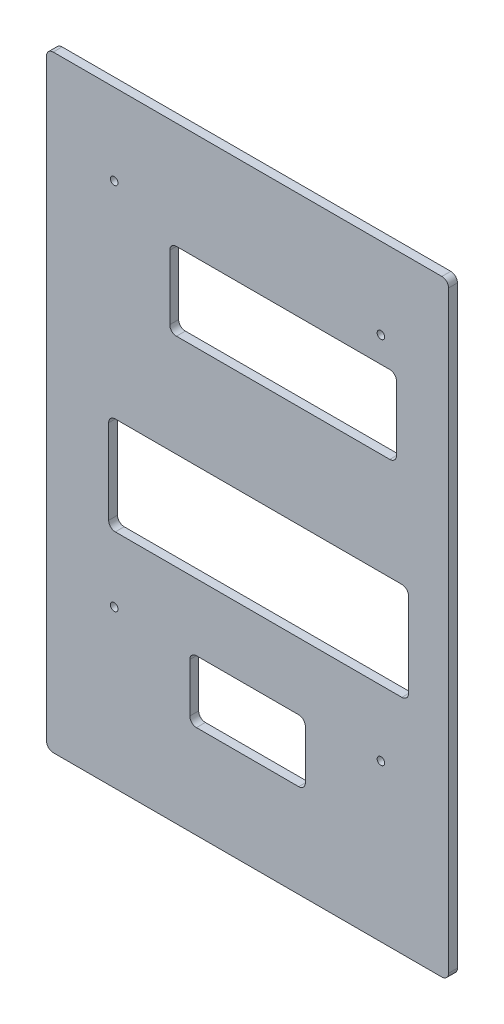
SolidWorks part; units mm, degrees
material "Verre"
ref_plane "Plan de face" through (0, 0, 0) normal (0, 0, 1) x (1, 0, 0)
ref_plane "Plan de dessus" through (0, 0, 0) normal (0, 1, 0) x (1, 0, 0)
ref_plane "Plan de droite" through (0, 0, 0) normal (1, 0, 0) x (0, 0, -1)
sketch "Esquisse1" plane through (0, 0, 0) normal (0, 0, 1) x (1, 0, 0)
  line L1 (0, 0) -> (180.86, 0)
  line L2 (0, 0) -> (0, 273)
  line L3 (0, 273) -> (180.86, 273)
  line L4 (180.86, 0) -> (180.86, 273)
  line L5 (64.43, 70) -> (116.43, 70)
  line L6 (64.43, 70) -> (64.43, 42)
  line L7 (64.43, 42) -> (116.43, 42)
  line L8 (116.43, 70) -> (116.43, 42)
  line L9 (27.93, 144) -> (162.86, 144)
  line L10 (27.93, 144) -> (27.93, 100)
  line L11 (27.93, 100) -> (162.86, 100)
  line L12 (162.86, 144) -> (162.86, 100)
  line L13 (55.43, 225) -> (157.43, 225)
  line L14 (55.43, 225) -> (55.43, 190)
  line L15 (55.43, 190) -> (157.43, 190)
  line L16 (157.43, 225) -> (157.43, 190)
  circle A0 centre (30.43, 236.5) radius 1.5
  circle A1 centre (150.43, 236.5) radius 1.5
  circle A2 centre (30.43, 70.5) radius 1.5
  circle A3 centre (150.43, 70.5) radius 1.5
  dimension "D5" = 3
  dimension "D8" = 3
  dimension "D13" = 3
  dimension "D14" = 3
  dimension "D1" = 180.86
  dimension "D2" = 273
  dimension "D3" = 30.43
  dimension "D4" = 36.5
  dimension "D6" = 36.5
  dimension "D7" = 30.43
  dimension "D9" = 30.43
  dimension "D10" = 30.43
  dimension "D11" = 70.5
  dimension "D12" = 70.5
  dimension "D15" = 64.43
  dimension "D16" = 42
  dimension "D17" = 28
  dimension "D18" = 30
  dimension "D19" = 44
  dimension "D20" = 52
  dimension "D21" = 27.93
  dimension "D22" = 18
  dimension "D23" = 48
  dimension "D24" = 35
  dimension "D25" = 55.43
  dimension "D26" = 102
extrude "Boss.-Extru.1" add sketch "Esquisse1" along normal blind 4
hole_wizard "Dégagement M31" positions "Esquisse2" profile "Esquisse3" hole size "M3" standard "ISO" end condition through all
sketch "Esquisse2" plane through (0, 0, 4) normal (0, 0, 1) x (1, 0, 0)
  point P0 (30.43, 236.5)
  point P3 (150.43, 236.5)
  point P6 (150.43, 70.5)
  point P9 (30.43, 70.5)
sketch "Esquisse3" plane through (30.43, 236.5, 4) normal (1, 0, 0) x (0, -1, 0)
  line L0 (0, 0) -> (0, 4)
  line L1 (0, 4) -> (1.7, 4)
  line L2 (1.7, 4) -> (1.7, 0)
  line L5 (1.7, 0) -> (0, 0)
  line L11 (0, -6.35) -> (0, 107.95) construction
  dimension "Diamètre du perçage jusqu'au prochain" = 3.4
  dimension "Profondeur du perçage jusqu'au prochain" = 4
fillet "Congé1" radius 3 16 edges at (0, 0, 2) (180.86, 0, 2) (116.43, 42, 2) (64.43, 42, 2) (116.43, 70, 2) (64.43, 70, 2) (162.86, 100, 2) (27.93, 100, 2) (162.86, 144, 2) (27.93, 144, 2) (180.86, 273, 2) (0, 273, 2) (157.43, 190, 2) (157.43, 225, 2) (55.43, 225, 2) (55.43, 190, 2)
sketch "Esquisse4" [suppressed] plane through (0, 0, 4) normal (0, 0, 1) x (1, 0, 0)
  line L0 (27.93, 165) -> (162.86, 165) construction
  line L1 (58.43, 190) -> (154.43, 190) construction
  line L3 (27.93, 165) -> (27.93, 135.3531) construction
  line L4 (162.86, 165) -> (162.86, 135.3531) construction
  line L5 (27.93, 141) -> (27.93, 103) construction
  line L6 (162.86, 103) -> (162.86, 141) construction
  point P5 (27.93, 135.3531)
  point P9 (162.86, 135.3531)
  dimension "D1" = 25
sketch "Esquisse5" plane through (0, 0, 0) normal (0, 0, -1) x (-1, 0, 0)
  line L0 (-56.9089, 202.3439) -> (421.0911, 202.3439) construction
  line L1 (107.0911, 240.8566) -> (1241.0911, 240.8566) construction
  line L2 (-94.2833, 174.0347) -> (-91.1852, 174.0347)
  line L3 (-91.1852, 174.0347) -> (-91.1824, 166.7906)
  line L4 (-84.6968, 170.3369) -> (-88.3318, 166.2594)
  line L5 (-88.3318, 166.2594) -> (-84.4535, 160.0184)
  line L6 (-84.4535, 160.0184) -> (-87.9228, 160.0184)
  line L7 (-87.9228, 160.0184) -> (-90.4278, 164.3432)
  line L8 (-91.1824, 160.0184) -> (-94.2833, 160.0184)
  line L9 (-94.2833, 160.0184) -> (-94.2833, 174.0347)
  line L10 (-78.7925, 174.0347) -> (-75.6893, 174.0347)
  line L11 (-75.6893, 174.0347) -> (-75.6893, 169.1495)
  line L12 (-69.5264, 160.0184) -> (-72.6249, 160.0184)
  line L13 (-75.6943, 160.0184) -> (-78.7925, 160.0184)
  line L14 (-78.7925, 160.0184) -> (-78.7925, 174.0347)
  line L15 (-139.2569, 172.9353) -> (-137.1581, 172.9353)
  line L16 (-137.1581, 172.9353) -> (-137.1581, 170.4368)
  line L17 (-137.1581, 170.4368) -> (-133.6735, 170.4368)
  line L18 (-133.6735, 170.4368) -> (-133.6735, 168.1381)
  line L19 (-133.6735, 168.1381) -> (-137.1581, 168.1381)
  line L20 (-137.1581, 168.1381) -> (-137.1581, 162.8704)
  line L21 (-133.2794, 162.5414) -> (-133.2794, 160.2428)
  line L22 (-140.1754, 168.1381) -> (-141.7532, 168.1381)
  line L23 (-141.7532, 168.1381) -> (-141.7532, 170.3369)
  line L24 (-141.7532, 170.3369) -> (-140.0239, 170.3369)
  line L25 (-140.0239, 170.3369) -> (-139.2569, 172.9353)
  line L26 (-12.9312, 172.9353) -> (-10.9324, 172.8354)
  line L27 (-10.9324, 172.8354) -> (-10.8324, 170.4368)
  line L28 (-10.8324, 170.4368) -> (-7.4344, 170.4368)
  line L29 (-7.4344, 170.4368) -> (-7.4344, 168.1381)
  line L30 (-7.4344, 168.1381) -> (-10.9324, 168.1381)
  line L31 (-10.9324, 168.1381) -> (-10.8324, 162.5414)
  line L32 (-57.505, 164.5403) -> (-59.1422, 164.5403)
  line L33 (-7.0347, 162.4415) -> (-7.0347, 160.2428)
  line L34 (-13.8145, 168.2381) -> (-15.4406, 168.2381)
  line L35 (-15.4406, 168.2381) -> (-15.4406, 170.4368)
  line L36 (-15.4406, 170.4368) -> (-13.7165, 170.4368)
  line L37 (-13.7165, 170.4368) -> (-12.9312, 172.9353)
  line L38 (-174.2363, 172.8354) -> (-163.6381, 172.8354)
  line L39 (-163.6381, 172.8354) -> (-163.6381, 170.2335)
  line L40 (-163.6381, 170.2335) -> (-167.3327, 170.2335)
  line L41 (-167.3327, 170.2335) -> (-167.3327, 160.0184)
  line L42 (-167.3327, 160.0184) -> (-170.5222, 160.0184)
  line L43 (-170.5222, 160.0184) -> (-170.5703, 170.2335)
  line L44 (-170.5703, 170.2335) -> (-174.2363, 170.2335)
  line L45 (-174.2363, 170.2335) -> (-174.2363, 172.8354)
  line L46 (-47.2135, 160.0661) -> (-47.2135, 172.8354)
  line L47 (-27.5226, 172.1358) -> (-25.224, 172.0359)
  line L48 (-25.224, 172.0359) -> (-24.9241, 170.6367)
  line L49 (-22.8254, 171.1364) -> (-21.1497, 169.4374)
  line L50 (-21.6333, 167.3283) -> (-20.2269, 167.1387)
  line L51 (-20.2269, 167.1387) -> (-20.3269, 164.8401)
  line L52 (-20.3269, 164.8401) -> (-21.726, 164.5403)
  line L53 (-21.3263, 162.4415) -> (-22.9253, 160.8424)
  line L54 (-22.9253, 160.8424) -> (-24.1246, 161.642)
  line L55 (-25.0241, 161.2422) -> (-25.3239, 159.843)
  line L56 (-25.3239, 159.843) -> (-27.5226, 159.943)
  line L57 (-27.5226, 159.943) -> (-27.8224, 161.3421)
  line L58 (-29.9212, 160.9424) -> (-31.5203, 162.5414)
  line L59 (-31.5203, 162.5414) -> (-30.7207, 163.7407)
  line L60 (-31.1205, 164.6402) -> (-32.5197, 164.94)
  line L61 (-32.5197, 164.94) -> (-32.4197, 167.1387)
  line L62 (-32.4197, 167.1387) -> (-31.0206, 167.4386)
  line L63 (-30.7207, 168.338) -> (-31.5203, 169.5373)
  line L64 (-31.5203, 169.5373) -> (-29.9212, 171.0364)
  line L65 (-27.8224, 170.6367) -> (-27.5226, 172.1358)
  line L66 (-121.3674, 171.736) -> (-113.2722, 160.1428)
  line L67 (-113.2722, 160.1428) -> (-130.1622, 160.2428)
  line L68 (-130.1622, 160.2428) -> (-121.3674, 171.736)
  line L69 (-101.122, 160.0184) -> (-104.166, 160.0184)
  line L70 (-107.2724, 160.0184) -> (-110.3739, 160.0184)
  line L71 (-110.3739, 160.0184) -> (-110.3739, 170.4368)
  line L72 (-110.3739, 170.4368) -> (-107.471, 170.4368)
  line L73 (-107.2724, 169.1495) -> (-107.471, 169.1495)
  line L74 (-55.5361, 159.943) -> (-54.06, 159.943)
  line L75 (-53.0008, 162.1272) -> (-53.0008, 160.2428)
  line L76 (-57.4815, 166.5394) -> (-57.4815, 167.3283)
  line L77 (-59.7101, 167.0388) -> (-62.9094, 167.1387)
  line L78 (-157.7434, 170.3369) -> (-154.6917, 170.352)
  line L79 (-151.8049, 170.352) -> (-148.7513, 170.3369)
  line L80 (-148.7513, 170.3369) -> (-148.6473, 160.0184)
  line L81 (-148.6473, 160.0184) -> (-151.6216, 160.0184)
  line L82 (-151.6216, 160.0184) -> (-151.6216, 161.4269)
  line L83 (-122.8785, 167.7334) -> (-124.9653, 161.2422)
  line L84 (-124.9653, 161.2422) -> (-127.9635, 161.3421)
  line L85 (-127.9635, 161.3421) -> (-122.8785, 167.7334)
  line L86 (-121.2675, 169.4374) -> (-115.4709, 161.3421)
  line L87 (-115.4709, 161.3421) -> (-123.6661, 161.3421)
  line L88 (-123.6661, 161.3421) -> (-121.2675, 169.4374)
  line L89 (-44.0087, 167.9383) -> (-44.0087, 170.3369)
  line L90 (-44.0267, 165.4648) -> (-44.0267, 162.5414)
  line L91 (-44.0267, 162.5414) -> (-41.8105, 162.5414)
  line L92 (-41.8105, 165.4648) -> (-44.0267, 165.4648)
  line L93 (-22.0456, 168.2381) -> (-21.1497, 169.4374)
  line L94 (-22.0456, 168.2381) -> (-21.6333, 167.3283)
  line L95 (-25.0241, 161.2422) -> (-24.1246, 161.642)
  line L96 (-31.1205, 164.6402) -> (-30.7207, 163.7407)
  line L97 (-30.7207, 168.338) -> (-31.0206, 167.4386)
  line L98 (-60.0892, 163.7407) -> (-60.0892, 162.8704)
  line L99 (-57.505, 164.5403) -> (-57.505, 163.8272)
  line L100 (-154.6917, 170.352) -> (-154.6917, 164.3054)
  line L101 (-151.8049, 170.352) -> (-151.8049, 164.3054)
  line L102 (-107.471, 169.1495) -> (-107.471, 170.4368)
  line L103 (-101.122, 160.0184) -> (-101.122, 167.4386)
  line L104 (-104.166, 160.0184) -> (-104.166, 165.9507)
  line L105 (-107.2724, 160.0184) -> (-107.2724, 165.9507)
  line L106 (-84.6968, 170.3369) -> (-88.0776, 170.3369)
  line L107 (-88.0776, 170.3369) -> (-91.1824, 166.7906)
  line L108 (-91.1824, 160.0184) -> (-91.1824, 163.8272)
  line L109 (-91.1824, 163.8272) -> (-90.4278, 164.3432)
  line L110 (-75.6943, 160.0184) -> (-75.6943, 165.9507)
  line L111 (-72.6249, 160.0184) -> (-72.6249, 166.7906)
  line L112 (-69.5264, 160.0184) -> (-69.5264, 167.4386)
  line L113 (-54.4145, 167.0061) -> (-54.4145, 162.6507)
  line L114 (-47.2135, 172.8354) -> (-41.5192, 172.8354)
  line L115 (-47.2135, 160.0661) -> (-40.67, 160.0661)
  line L116 (-44.0087, 170.3369) -> (-42.1743, 170.3369)
  line L117 (-44.0087, 167.9383) -> (-42.0498, 167.9383)
  arc A0 (-59.1422, 164.5403) -> (-60.0892, 163.7407) centre (-59.1422, 163.5797) ccw
  circle A1 centre (-26.3868, 165.9832) radius 2.3707
  arc A2 (-41.8105, 162.5414) -> (-41.8105, 165.4648) centre (-41.8105, 164.0031) ccw
  spline S0 degree 3 poles (-75.6943, 165.9507) (-75.607, 166.6089) (-75.1986, 167.568) (-73.6088, 168.4964) (-72.5255, 167.5211) (-72.6249, 166.7906) knots 0 0 0 0 0.394541 0.59607 1 1 1 1
  spline S1 degree 3 poles (-75.6893, 169.1495) (-75.2594, 169.7597) (-73.9101, 170.5281) (-70.9079, 170.7231) (-69.5421, 168.6416) (-69.5264, 167.4386) knots 0 0 0 0 0.262741 0.558365 1 1 1 1
  spline S2 degree 3 poles (-54.4145, 162.6507) (-54.3978, 162.4449) (-54.1312, 161.7319) (-53.3221, 162.0376) (-53.0008, 162.1272) knots 0 0 0 0 0.373122 1 1 1 1
  spline S3 degree 3 poles (-57.0864, 161.3421) (-56.9419, 160.6025) (-56.2449, 160.0799) (-55.5361, 159.943) knots 0 0 0 0 1 1 1 1
  spline S4 degree 3 poles (-137.1581, 162.8704) (-137.1357, 162.6205) (-136.8298, 162.3293) (-135.4596, 161.9489) (-134.2298, 162.3066) (-133.2794, 162.5414) knots 0 0 0 0 0.163675 0.27749 1 1 1 1
  spline S5 degree 3 poles (-133.2794, 160.2428) (-134.8141, 160.051) (-138.7019, 159.2323) (-139.6757, 161.3421) (-139.8081, 161.6291) (-139.9498, 161.9266) (-139.9755, 162.2416) (-140.1355, 164.2017) (-140.072, 166.1742) (-140.1754, 168.1381) knots 0 0 0 0 1 1 1 2 2 2 3 3 3 3
  spline S6 degree 3 poles (-7.0347, 160.2428) (-8.6244, 160.0676) (-12.4699, 159.3084) (-13.4142, 161.4355) (-13.624, 161.9082) (-13.782, 162.4232) (-13.792, 162.9403) (-13.826, 164.7059) (-13.807, 166.4722) (-13.8145, 168.2381) knots 0 0 0 0 1 1 1 2 2 2 3 3 3 3
  spline S7 degree 3 poles (-40.67, 160.0661) (-39.7367, 160.1577) (-38.4804, 160.8468) (-37.2595, 162.3426) (-37.1701, 163.6675) (-37.1743, 165.538) (-38.7166, 166.4794) (-39.5286, 166.7906) knots 0 0 0 0 0.282707 0.43558 0.571416 0.685536 1 1 1 1
  spline S8 degree 3 poles (-39.5286, 166.7906) (-38.9565, 166.948) (-38.2374, 167.6832) (-37.8968, 168.9733) (-37.8113, 170.1278) (-38.2848, 171.2576) (-39.48, 172.3911) (-40.6921, 172.7767) (-41.5192, 172.8354) knots 0 0 0 0 0.199158 0.317575 0.451003 0.584991 0.71822 1 1 1 1
  spline S9 degree 3 poles (-24.9241, 170.6367) (-23.5477, 170.1779) (-23.8936, 170.4242) (-22.8254, 171.1364) knots 0 0 0 0 1 1 1 1
  spline S10 degree 3 poles (-21.726, 164.5403) (-22.2066, 163.0985) (-21.9033, 163.5956) (-21.3263, 162.4415) knots 0 0 0 0 1 1 1 1
  spline S11 degree 3 poles (-27.8224, 161.3421) (-28.7992, 161.6677) (-28.5552, 161.7587) (-29.2216, 161.3421) (-29.4494, 161.1998) (-29.688, 161.0756) (-29.9212, 160.9424) knots 0 0 0 0 1 1 1 2 2 2 2
  spline S12 degree 3 poles (-29.9212, 171.0364) (-29.4943, 170.8941) (-29.1686, 170.3865) (-28.7219, 170.3369) (-28.3801, 170.2989) (-28.1209, 170.5372) (-27.8224, 170.6367) knots 0 0 0 0 1 1 1 2 2 2 2
  spline S13 degree 3 poles (-107.2724, 169.1495) (-106.8585, 169.8299) (-105.5179, 170.598) (-103.5202, 170.6358) (-101.6572, 169.6874) (-101.1521, 168.2861) (-101.122, 167.4386) knots 0 0 0 0 0.27864 0.525252 0.687769 1 1 1 1
  spline S14 degree 3 poles (-107.2724, 165.9507) (-107.2465, 166.745) (-106.2762, 168.5882) (-104.0431, 167.7417) (-104.2041, 166.4557) (-104.166, 165.9507) knots 0 0 0 0 0.496685 0.694227 1 1 1 1
  spline S15 degree 2 poles (-54.06, 159.943) (-53.5081, 160.0158) (-53.0008, 160.2428) knots 0 0 0 1 1 1
  spline S16 degree 3 poles (-59.7101, 167.0388) (-59.773, 167.4531) (-59.3518, 168.8785) (-57.4745, 168.3639) (-57.4815, 167.3283) knots 0 0 0 0 0.367002 1 1 1 1
  spline S17 degree 3 poles (-57.0864, 161.3421) (-57.3774, 161.0516) (-57.8191, 160.5577) (-58.1867, 160.3437) (-59.3607, 159.6603) (-61.068, 159.6271) (-62.1842, 160.4472) (-63.7018, 161.5622) (-63.6714, 164.6228) (-62.0796, 165.6441) (-60.7256, 166.5129) (-59.0024, 166.4238) (-57.4815, 166.5394) knots 0 0 0 0 1 1 1 2 2 2 3 3 3 4 4 4 4
  spline S18 degree 3 poles (-62.9094, 167.1387) (-62.8636, 167.8511) (-62.16, 169.9427) (-59.8154, 170.6023) (-58.5702, 170.5768) knots 0 0 0 0 0.353066 1 1 1 1
  spline S19 degree 3 poles (-154.6917, 164.3054) (-154.7394, 163.7332) (-154.5444, 163.0059) (-153.7633, 162.1776) (-152.8735, 162.3733) (-152.0344, 163.0441) (-151.8568, 163.8566) (-151.8049, 164.3054) knots 0 0 0 0 0.303187 0.415254 0.583999 0.737935 1 1 1 1
  spline S20 degree 3 poles (-151.6216, 161.4269) (-151.9172, 161.1229) (-152.1728, 160.7741) (-152.5084, 160.515) (-152.7443, 160.3329) (-153.0209, 160.2022) (-153.3023, 160.1041) (-155.6394, 159.2885) (-157.5509, 160.7972) (-157.6441, 163.2417) (-157.7341, 165.6053) (-157.7103, 167.9718) (-157.7434, 170.3369) knots 0 0 0 0 1 1 1 2 2 2 3 3 3 4 4 4 4
  spline S21 degree 3 poles (-42.0498, 167.9383) (-41.6698, 167.9271) (-41.2486, 168.3464) (-41.0744, 169.1173) (-41.2166, 169.9639) (-41.8255, 170.2992) (-42.1743, 170.3369) knots 0 0 0 0 0.294875 0.472372 0.68529 1 1 1 1
  spline S23 degree 3 poles (-7.0347, 162.4415) (-7.8006, 162.2378) (-9.0559, 162.1282) (-10.4545, 162.0729) (-10.8324, 162.5414) knots 0 0 0 0 0.590902 1 1 1 1
  spline S24 degree 3 poles (-57.505, 163.8272) (-57.5306, 163.3193) (-57.9984, 162.5511) (-59.1839, 162.1257) (-60.0621, 162.2684) (-60.0892, 162.8704) knots 0 0 0 0 0.406447 0.637072 1 1 1 1
  spline S25 degree 3 poles (-54.4145, 167.0061) (-54.3865, 167.6214) (-54.6519, 168.6026) (-55.5308, 169.6381) (-56.7202, 170.5068) (-57.8839, 170.5371) (-58.5702, 170.5768) knots 0 0 0 0 0.300061 0.46914 0.655769 1 1 1 1
ref_plane "Plan1" [suppressed] through (0, 0, 2) normal (0, 0, 1) x (1, 0, 0)
extrude "Enlèv. mat.-Extru.2" cut sketch "Esquisse5" against normal blind 1
equation "\"D7@Esquisse1\"=\"D3@Esquisse1\""
equation "\"D9@Esquisse1\"=\"D3@Esquisse1\""
equation "\"D10@Esquisse1\"=\"D3@Esquisse1\""
equation "\"D12@Esquisse1\"=\"D11@Esquisse1\""
equation "\"D13@Esquisse1\"=\"D5@Esquisse1\""
equation "\"D14@Esquisse1\"=\"D8@Esquisse1\""
